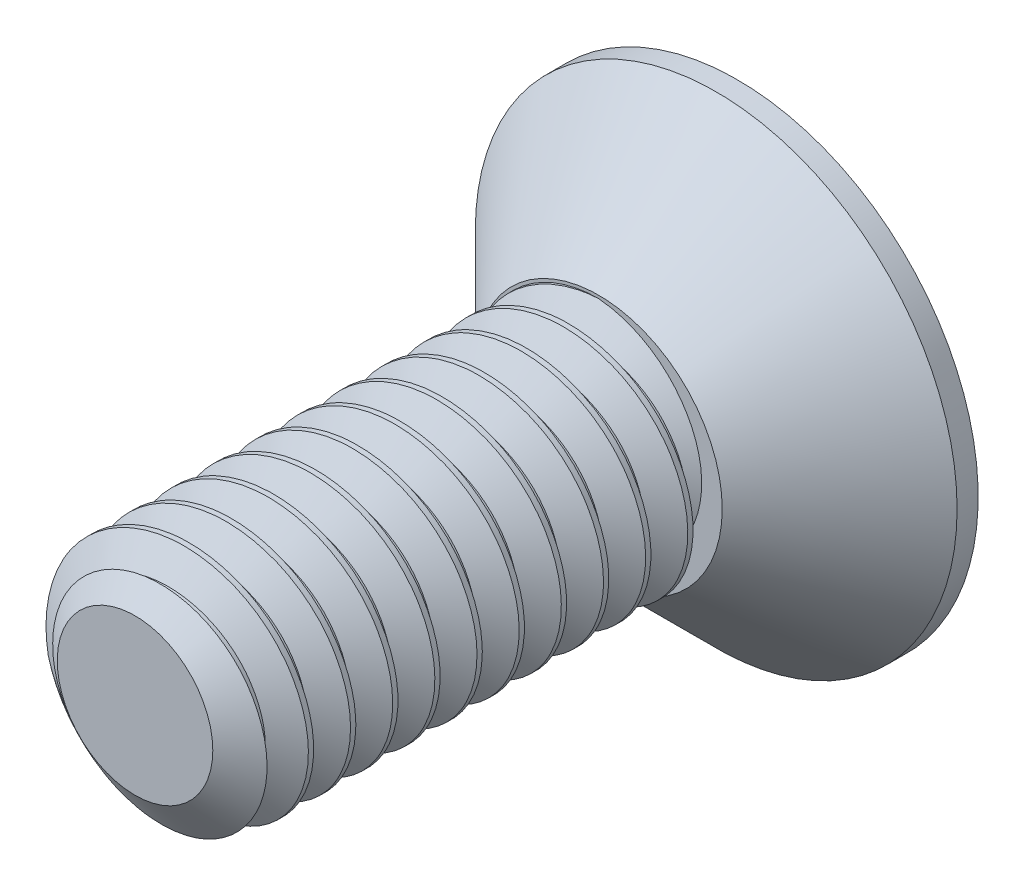
SolidWorks part; units mm, degrees
ref_plane "Front Plane" through (0, 0, 0) normal (0, 0, 1) x (1, 0, 0)
ref_plane "Top Plane" through (0, 0, 0) normal (0, 1, 0) x (1, 0, 0)
ref_plane "Right Plane" through (0, 0, 0) normal (1, 0, 0) x (0, 0, -1)
sketch "Sketch1" plane through (0, 0, 0) normal (0, 0, 1) x (1, 0, 0)
  circle A0 centre (0, 0) radius 2
  dimension "OD" = 4
extrude "Extrude1" add sketch "Sketch1" against normal blind 10
sketch "Sketch2" plane through (0, 0, 0) normal (0, 0, 1) x (1, 0, 0)
  circle A0 centre (0, 0) radius 2 construction
  circle A1 centre (0, 0) radius 2
curve "Helix/Spiral1" pitch 0.7 height 10.7 radius 2 centre (0, 0, 0) axis (0, 0, -1) start towards (0, 1, 0) parameters "pitch"=0.7
sketch "Sketch3" plane through (0, 0, 0) normal (1, 0, 0) x (0, 0, -1)
  line L0 (-0.6125, 2) -> (-0.35, 1.5453)
  line L1 (-0.35, 1.5453) -> (-0.2625, 1.5453)
  line L2 (-0.2625, 1.5453) -> (0, 2)
  line L3 (-0.6125, 2) -> (0, 2)
  line L4 (-0.3063, 2) -> (-0.3063, 1.5453) construction
  line L5 (-0.4813, 1.7727) -> (-0.1313, 1.7727) construction
  line L6 (0, 2) -> (0, -2) construction
  dimension "D1" = 0.0875
  dimension "D2" = 0.35
  dimension "D3" = 60
sweep "Cut-Sweep1" cut profiles "Sketch3" path "Helix/Spiral1"
sketch "Sketch4" plane through (0, 0, 0) normal (1, 0, 0) x (0, 0, -1)
  line L0 (0.4962, 2) -> (0, 1.2913)
  line L1 (0, 1.2913) -> (0, 2)
  line L2 (0.4962, 2) -> (0, 2)
  line L3 (-0.6125, 2) -> (0, 2) construction
  line L4 (0, 0) -> (7.0209, 0) construction
  dimension "D1" = 55
  dimension "D2" = 0.254
revolve "Cut-Revolve1" cut sketch "Sketch4" angle 360 about L4
sketch "Sketch5" plane through (0, 0, 0) normal (1, 0, 0) x (0, 0, -1)
  line L0 (10, 0.3311) -> (10, 1.814) construction
  line L1 (10, 2.05) -> (18.1906, 2.05)
  line L2 (10, 2.05) -> (10, 0)
  line L3 (10, 0) -> (18, 0)
  line L4 (18, 1.7198) -> (18, 0)
  line L5 (18.1906, 2.05) -> (18, 1.7198)
  line L6 (0, 0) -> (9.9695, 0) construction
  point P3 (18, 2.05)
  point P10 (18, 2.05)
  dimension "D1" = 0.3302
  dimension "Thread min" = 18
  dimension "D2" = 0.05
  dimension "D3" = 30
revolve "partially thread" [suppressed] add sketch "Sketch5" angle 360 about L6
sketch "Sketch6" plane through (0, 0, -10) normal (0, 0, -1) x (-1, 0, 0)
  circle A0 centre (0, 0) radius 4
  dimension "head dia" = 8
extrude "Extrude2" add sketch "Sketch6" against normal blind 2.3
sketch "Sketch10" plane through (0, 0, 0) normal (1, 0, 0) x (0, 0, -1)
  line L0 (9.65, -4) -> (7.7, -2.05)
  line L1 (7.7, -2.05) -> (7.7, -4)
  line L2 (9.65, -4) -> (7.7, -4)
  line L3 (0, 0) -> (7.7, 0) construction
  line L4 (7.7, 4) -> (7.7, -4) construction
  line L5 (9.65, 4) -> (7.7, 4) construction
  line L6 (7.7, 2.05) -> (7.7, 4) construction
  line L7 (9.65, 4) -> (7.7, 2.05) construction
  line L8 (7.7, 4) -> (7.7, -4) construction
  line L9 (7.7, 2.05) -> (7.7, -2.05) construction
  dimension "D1" = 45
  dimension "D2" = 0.05
revolve "Cut-Revolve2" cut sketch "Sketch10" angle 360 about L3
sketch "Sketch11" [suppressed] plane through (0, 0, 0) normal (1, 0, 0) x (0, 0, -1)
  line L0 (-0.35, 1.5453) -> (-0.2625, 1.5453) construction
  line L1 (9.65, 4) -> (7.7, 2.05) construction
  line L2 (6.4816, 1.5453) -> (6.4816, 0)
  line L3 (6.4816, 0) -> (7.7, 0)
  line L4 (7.7, 2.05) -> (7.7, 0)
  line L5 (0, 0) -> (7.7, 0) construction
  arc A0 (7.7, 2.05) -> (6.4816, 1.5453) centre (6.4816, 3.2684) cw
revolve "Revolve1" [suppressed] add sketch "Sketch11" angle 360 about L3
sketch "Sketch7" plane through (0, 0, -10) normal (0, 0, 1) x (1, 0, 0)
  line L1 (0, 1.4434) -> (-1.25, 0.7217)
  line L2 (-1.25, 0.7217) -> (-1.25, -0.7217)
  line L3 (-1.25, -0.7217) -> (0, -1.4434)
  line L4 (0, -1.4434) -> (1.25, -0.7217)
  line L5 (1.25, -0.7217) -> (1.25, 0.7217)
  line L6 (1.25, 0.7217) -> (0, 1.4434)
  circle A0 centre (0, 0) radius 1.25 construction
  dimension "hex dia" = 2.5
extrude "Cut-Extrude1" cut sketch "Sketch7" along normal blind 1.875
sketch "Sketch8" plane through (0, 0, -10) normal (0, 0, 1) x (1, 0, 0)
  circle A0 centre (0, 0) radius 1.4434
extrude "Cut-Extrude2" cut sketch "Sketch8" along normal through all draft 45
sketch "Sketch9" [suppressed] plane through (0, 0, 0) normal (1, 0, 0) x (0, 0, -1)
  line L0 (0, 2) -> (0, -2) construction
  line L1 (3.85, 2) -> (3.85, -2) construction
  line L2 (7.7, 2) -> (7.7, -2) construction
  line L3 (7.7, -2.05) -> (7.7, -4) construction
  dimension "D1" = 3.85
equation "\"D3@Helix/Spiral1\" = \"screw length@Extrude1\"+\"pitch@Helix/Spiral1\""
equation "\"D1@Sketch3\" = \"pitch@Helix/Spiral1\"*.125"
equation "\"D2@Sketch3\" = \"pitch@Helix/Spiral1\"*.5"
equation "\"D1@Cut-Extrude1\" = \"hex dia@Sketch7\"*.75"
equation "\"D1@Sketch9\" = \"pitch@Helix/Spiral1\"*5.5"
equation "\"D2@Sketch10\" = \"D2@Sketch5\""
